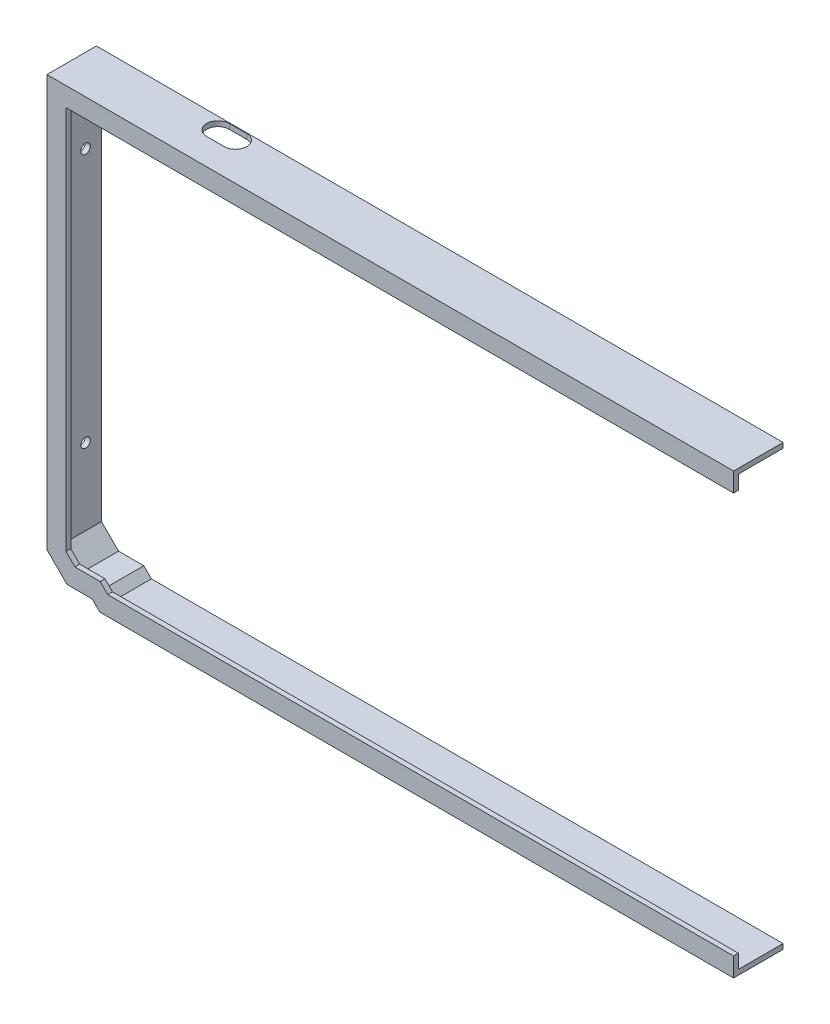
SolidWorks part; units mm, degrees
ref_plane "Přední rovina" through (0, 0, 0) normal (0, 0, 1) x (1, 0, 0)
ref_plane "Horní rovina" through (0, 0, 0) normal (0, 1, 0) x (1, 0, 0)
ref_plane "Pravá rovina" through (0, 0, 0) normal (1, 0, 0) x (0, 0, -1)
sketch "Skica1" plane through (0, 0, 0) normal (0, 0, 1) x (1, 0, 0)
  line L0 (0, 0) -> (428.28, 0) construction
  line L1 (0, 0) -> (0, -126.92) construction
  line L2 (428.28, 0) -> (428.28, -126.92) construction
  line L3 (0, -126.92) -> (5.3104, -132.2304) construction
  line L4 (428.28, -126.92) -> (422.9696, -132.2304) construction
  line L5 (5.3104, -132.2304) -> (13.2504, -132.2304) construction
  line L6 (422.9696, -132.2304) -> (415.0296, -132.2304) construction
  line L7 (13.2504, -132.2304) -> (15.6333, -134.6133) construction
  line L8 (415.0296, -132.2304) -> (412.6467, -134.6133) construction
  line L9 (412.6467, -134.6133) -> (15.6333, -134.6133) construction
  line L10 (-0.1, 0.1) -> (428.38, 0.1)
  line L11 (428.38, 0.1) -> (428.38, -126.9614)
  line L12 (428.38, -126.9614) -> (423.011, -132.3304)
  line L13 (423.011, -132.3304) -> (415.071, -132.3304)
  line L14 (415.071, -132.3304) -> (412.6881, -134.7133)
  line L15 (412.6881, -134.7133) -> (15.5919, -134.7133)
  line L16 (13.209, -132.3304) -> (15.5919, -134.7133)
  line L17 (5.269, -132.3304) -> (13.209, -132.3304)
  line L18 (-0.1, -126.9614) -> (5.269, -132.3304)
  line L19 (-0.1, 0.1) -> (-0.1, -126.9614)
  line L20 (-1.7, 1.7) -> (429.98, 1.7)
  line L21 (429.98, 1.7) -> (429.98, -127.6242)
  line L22 (429.98, -127.6242) -> (423.6738, -133.9304)
  line L23 (423.6738, -133.9304) -> (415.7338, -133.9304)
  line L24 (415.7338, -133.9304) -> (413.3508, -136.3133)
  line L25 (413.3508, -136.3133) -> (14.9292, -136.3133)
  line L26 (12.5462, -133.9304) -> (14.9292, -136.3133)
  line L27 (4.6062, -133.9304) -> (12.5462, -133.9304)
  line L28 (-1.7, -127.6242) -> (4.6062, -133.9304)
  line L29 (-1.7, 1.7) -> (-1.7, -127.6242)
  dimension "D1" = 428.28
  dimension "D2" = 126.92
  dimension "D3" = 126.92
  dimension "D4" = 7.51
  dimension "D5" = 7.51
  dimension "D6" = 135
  dimension "D7" = 135
  dimension "D8" = 7.94
  dimension "D9" = 7.94
  dimension "D10" = 3.37
  dimension "D11" = 3.37
  dimension "D12" = 135
  dimension "D13" = 0.1
  dimension "D14" = 1.6
extrude "Přidat vysunutím1" add sketch "Skica1" against normal blind 14.05
sketch "Skica2" plane through (0, 0, 0) normal (0, 0, 1) x (1, 0, 0)
  line L20 (4.3, -4.3) -> (4.3, -125.1389)
  line L21 (4.3, -125.1389) -> (7.0915, -127.9304)
  line L22 (7.0915, -127.9304) -> (15.0315, -127.9304)
  line L23 (15.0315, -127.9304) -> (17.4144, -130.3133)
  line L24 (17.4144, -130.3133) -> (410.8656, -130.3133)
  line L25 (410.8656, -130.3133) -> (413.2485, -127.9304)
  line L26 (413.2485, -127.9304) -> (421.1885, -127.9304)
  line L27 (421.1885, -127.9304) -> (423.98, -125.1389)
  line L28 (423.98, -125.1389) -> (423.98, -4.3)
  line L29 (423.98, -4.3) -> (4.3, -4.3)
  line L30 (4.3, -4.3) -> (4.3, -125.1389)
  line L31 (4.3, -125.1389) -> (7.0915, -127.9304)
  line L32 (7.0915, -127.9304) -> (15.0315, -127.9304)
  line L33 (15.0315, -127.9304) -> (17.4144, -130.3133)
  line L34 (17.4144, -130.3133) -> (410.8656, -130.3133)
  line L35 (410.8656, -130.3133) -> (413.2485, -127.9304)
  line L36 (413.2485, -127.9304) -> (421.1885, -127.9304)
  line L37 (421.1885, -127.9304) -> (423.98, -125.1389)
  line L38 (423.98, -125.1389) -> (423.98, -4.3)
  line L39 (423.98, -4.3) -> (4.3, -4.3)
  line L50 (-1.7, 1.7) -> (-1.7, -127.6242)
  line L51 (-1.7, -127.6242) -> (4.6062, -133.9304)
  line L52 (4.6062, -133.9304) -> (12.5462, -133.9304)
  line L53 (12.5462, -133.9304) -> (14.9292, -136.3133)
  line L54 (14.9292, -136.3133) -> (413.3508, -136.3133)
  line L55 (413.3508, -136.3133) -> (415.7338, -133.9304)
  line L56 (415.7338, -133.9304) -> (423.6738, -133.9304)
  line L57 (423.6738, -133.9304) -> (429.98, -127.6242)
  line L58 (429.98, -127.6242) -> (429.98, 1.7)
  line L59 (429.98, 1.7) -> (-1.7, 1.7)
  line L60 (-1.7, 1.7) -> (-1.7, -127.6242)
  line L61 (-1.7, -127.6242) -> (4.6062, -133.9304)
  line L62 (4.6062, -133.9304) -> (12.5462, -133.9304)
  line L63 (12.5462, -133.9304) -> (14.9292, -136.3133)
  line L64 (14.9292, -136.3133) -> (413.3508, -136.3133)
  line L65 (413.3508, -136.3133) -> (415.7338, -133.9304)
  line L66 (415.7338, -133.9304) -> (423.6738, -133.9304)
  line L67 (423.6738, -133.9304) -> (429.98, -127.6242)
  line L68 (429.98, -127.6242) -> (429.98, 1.7)
  line L69 (429.98, 1.7) -> (-1.7, 1.7)
  dimension "D1" = 6
  dimension "D2" = 0
extrude "Přidat vysunutím2" add sketch "Skica2" along normal blind 1.5
sketch "Skica3" plane through (0, 1.7, 0) normal (0, 1, 0) x (1, 0, 0)
  line L0 (-1.7, 10.3) -> (43.01, 10.3) construction
  line L1 (-1.7, 14.05) -> (-1.7, -1.5) construction
  line L2 (429.98, -1.5) -> (-1.7, -1.5) construction
  line L3 (45.76, 10.3) -> (40.26, 10.3) construction
  line L4 (45.76, 6.75) -> (40.26, 6.75)
  line L5 (45.76, 13.85) -> (40.26, 13.85)
  arc A0 (45.76, 6.75) -> (45.76, 13.85) centre (45.76, 10.3) ccw
  arc A1 (40.26, 13.85) -> (40.26, 6.75) centre (40.26, 10.3) ccw
  point P6 (40.26, 10.3)
  point P9 (43.01, 10.3)
  dimension "D5" = 3.55
  dimension "D1" = 11.8
  dimension "D2" = 44.71
  dimension "D3" = 2.75
  dimension "D4" = 7.1
extrude "Odebrat vysunutím1" cut sketch "Skica3" against normal up to surface (1.6 mm away) up to face at (214.14, 0.1, -7.025)
sketch "Skica4" plane through (-1.7, 0, 0) normal (-1, 0, 0) x (0, 0, 1)
  line L0 (-14.05, -62.9621) -> (1.5, -62.9621) construction
  line L1 (-14.05, 1.7) -> (-14.05, -127.6242) construction
  line L2 (1.5, 1.7) -> (1.5, -127.6242) construction
  circle A0 centre (-9.05, -22.9621) radius 1.5
  circle A1 centre (-9.05, -102.9621) radius 1.5
  dimension "D2" = 3
  dimension "D3" = 3
  dimension "D1" = 40
  dimension "D4" = 5
extrude "Odebrat vysunutím2" cut sketch "Skica4" against normal up to surface (431.68 mm away) up to face at (429.98, -62.9621, -6.275)
sketch "Skica5" plane through (0, 1.7, 0) normal (0, 1, 0) x (1, 0, 0)
  line L0 (429.98, -1.5) -> (-1.7, -1.5) construction
  line L1 (214.14, -1.5) -> (429.98, -1.5)
  line L2 (214.14, -1.5) -> (214.14, 14.05)
  line L3 (214.14, 14.05) -> (429.98, 14.05)
  line L4 (429.98, -1.5) -> (429.98, 14.05)
extrude "Odebrat vysunutím3" cut sketch "Skica5" against normal through all
